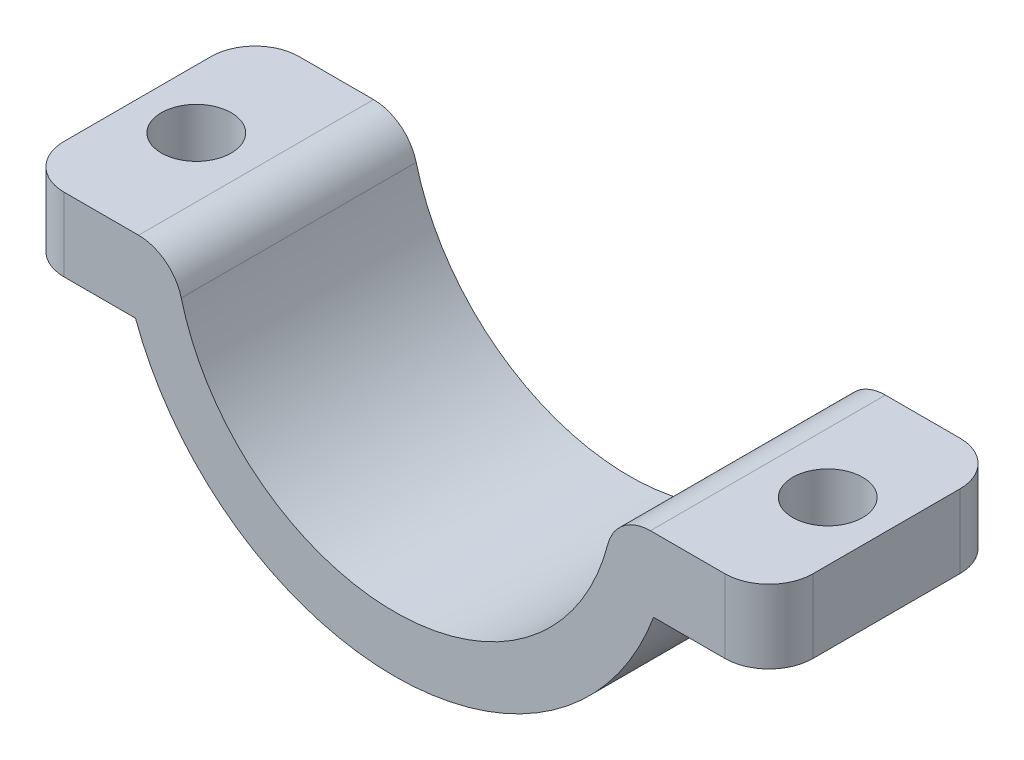
SolidWorks part; units mm, degrees
ref_plane "Alzado" through (0, 0, 0) normal (0, 0, 1) x (1, 0, 0)
ref_plane "Planta" through (0, 0, 0) normal (0, 1, 0) x (1, 0, 0)
ref_plane "Vista lateral" through (0, 0, 0) normal (1, 0, 0) x (0, 0, -1)
sketch "Croquis1" plane through (0, 0, 0) normal (0, 0, 1) x (1, 0, 0)
  line L0 (29.1365, 0) -> (-34.4299, 0) construction
  line L1 (-11.5, -1.5) -> (-25.5, -1.5)
  line L2 (-11.5, -1.5) -> (-11.5, -6.5)
  line L3 (-11.5, -6.5) -> (-25.5, -6.5)
  line L4 (-25.5, -1.5) -> (-25.5, -6.5)
  line L9 (0, 11.3797) -> (0, -23.4351) construction
  line L10 (11.5, -6.5) -> (25.5, -6.5)
  line L11 (-23.8813, -5.5) -> (-19.1187, -5.5) construction
  line L12 (-23.8813, -5.5) -> (-23.8813, -2.5) construction
  line L13 (-23.8813, -2.5) -> (-19.1187, -2.5) construction
  line L14 (-19.1187, -5.5) -> (-19.1187, -2.5) construction
  line L15 (-23.8813, -5.5) -> (-19.1187, -2.5) construction
  line L16 (-23.8813, -2.5) -> (-19.1187, -5.5) construction
  line L17 (25.5, -1.5) -> (25.5, -6.5)
  line L18 (11.5, -1.5) -> (25.5, -1.5)
  line L19 (11.5, -1.5) -> (11.5, -6.5)
  circle A0 centre (0, 0) radius 15
  circle A1 centre (0, 0) radius 18.8
  point P13 (-21.5, -4)
  dimension "D2" = 30
  dimension "D1" = 1.5
  dimension "D3" = 25.5
  dimension "D4" = 14
  dimension "D5" = 5
  dimension "D7" = 4.7625
  dimension "D8" = 4
  dimension "D9" = 2.5
  dimension "D10" = 3
  dimension "D6" = 3.8
extrude "Saliente-Extruir1" add sketch "Croquis1" along normal mid plane 16 contours A1 L10 L17 L18 | L10 A1 L18 A0 | L3 A1 L10 A0 | L1 A1 L3 A0 | A1 L1 L4 L3 region at (-16.3361, -4.032, 0) region at (-21.8978, -4.0635, 0) region at (0, -15.3736, 0) region at (16.3361, -4.032, 0) region at (21.8978, -4.0635, 0)
sketch "Croquis2" plane through (0, -1.5, 0) normal (0, 1, 0) x (1, 0, 0)
  line L0 (33.8639, 0) -> (-39.883, 0) construction
  line L1 (0, 13.5336) -> (0, -15.2197) construction
  line L2 (-25.5, -8) -> (-25.5, 8) construction
  circle A0 centre (-21.5, 0) radius 2.3813
  circle A1 centre (21.5, 0) radius 2.3813
  dimension "D2" = 4.7625
  dimension "D1" = 4
extrude "Cortar-Extruir1" cut sketch "Croquis2" against normal blind 16
fillet "Redondeo1" radius 3 6 edges at (14.9248, -1.5, 0) (-14.9248, -1.5, 0) (-25.5, -4, 8) (-25.5, -4, -8) (25.5, -4, -8) (25.5, -4, 8)
